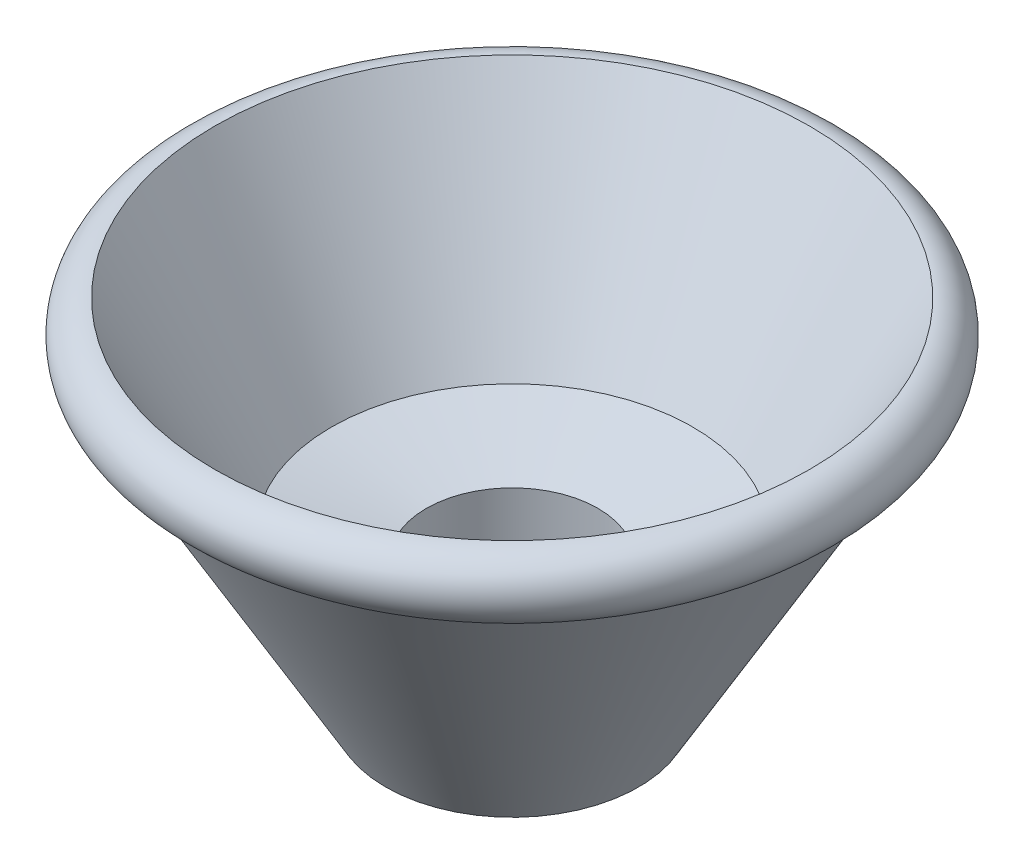
SolidWorks part; units mm, degrees
ref_plane "前视基准面" through (0, 0, 0) normal (0, 0, 1) x (1, 0, 0)
ref_plane "上视基准面" through (0, 0, 0) normal (0, 1, 0) x (1, 0, 0)
ref_plane "右视基准面" through (0, 0, 0) normal (1, 0, 0) x (0, 0, -1)
sketch "草图2" plane through (0, 0, 0) normal (0, 0, 1) x (1, 0, 0)
  line L0 (0, -55.2667) -> (0, 55.2667) construction
  line L1 (0, 0) -> (-4.6188, 8)
  line L4 (-4.6188, 8) -> (0, 8)
  line L5 (0, 8) -> (0, 0)
  point P4 (0, 0)
  dimension "D1" = 30
  dimension "D2" = 8
  dimension "D3" = 4.6188
revolve "旋转1" add sketch "草图2" angle 360 about L0
sketch "草图4" plane through (0, 0, 0) normal (0, 0, 1) x (1, 0, 0)
  line L0 (0, 7.1952) -> (0, 8.8048) construction
  line L2 (0, 8) -> (-4.0415, 8)
  line L3 (4.6188, 8) -> (-4.6188, 8) construction
  line L4 (-4.0415, 8) -> (0, 1)
  line L5 (0, 1) -> (0, 8)
  point P3 (0, 8)
  dimension "D1" = 30
  dimension "D2" = 7
sketch "草图5" plane through (0, 0, 0) normal (0, 1, 0) x (1, 0, 0)
  circle A0 centre (0, 0) radius 0.31
  dimension "D1" = 0.62
extrude "凸台-拉伸1" add sketch "草图5" against normal blind 6 and the other way blind 0.6
sketch "草图7" plane through (0, -6, 0) normal (0, -1, 0) x (1, 0, 0)
  circle A0 centre (0, 0) radius 0.28
  dimension "D1" = 0.56
extrude "切除-拉伸2" cut sketch "草图7" against normal through all
revolve "切除-旋转2" cut sketch "草图4" angle 360 about L0
sketch "草图10" plane through (0, 0, 0) normal (0, 0, 1) x (1, 0, 0)
  line L0 (-4.6188, 8) -> (-4.6188, 9) construction
  line L1 (-4.6188, 9) -> (4.6188, 8) construction
  line L2 (4.6188, 8) -> (4.6188, 9) construction
  line L3 (4.6188, 9) -> (-4.6188, 9) construction
  line L4 (-4.6188, 8.5) -> (4.9727, 8.5) construction
  line L5 (-4.6188, 8) -> (-4.0415, 8)
  line L6 (-4.0415, 8) -> (-4.0415, 9)
  line L7 (-4.0415, 9) -> (-4.6188, 9)
  line L8 (0, 0) -> (0, 12.6323) construction
  arc A0 (-4.6188, 9) -> (-4.6188, 8) centre (-4.6188, 8.5) ccw
  dimension "D1" = 1
revolve "旋转3" add sketch "草图10" angle 360 about L8 region at (-4.5329, 8.5, 0)
sketch "草图11" plane through (0, 0, 0) normal (0, 0, 1) x (1, 0, 0)
  line L0 (0, 0) -> (0, 13.3083) construction
  line L1 (-4.0415, 8) -> (-4.9325, 9.5433)
  line L2 (-4.9325, 9.5433) -> (-1.7812, 9.5433)
  line L3 (-1.7812, 9.5433) -> (-1.7812, 8)
  line L4 (-1.7812, 8) -> (-4.0415, 8)
  dimension "D1" = 30
revolve "切除-旋转3" cut sketch "草图11" angle 360 about L0
sketch "草图14" plane through (0, 0, 0) normal (0, 0, 1) x (1, 0, 0)
  line L0 (-0.325, 3.4014) -> (-0.325, 3.7514) construction
  line L1 (-4.6188, 8) -> (-0.31, 0.5369) construction
  line L2 (-0.325, 3.7514) -> (-2.1659, 3.7514) construction
  line L3 (0.325, 3.4014) -> (0.325, 3.7514)
  line L4 (-0.325, 3.4014) -> (0.325, 3.4014) construction
  line L5 (0.325, 3.7514) -> (2.1659, 3.7514)
  line L7 (0, 0) -> (0, 6.3714) construction
  line L9 (0.31, 0.5369) -> (4.6188, 8) construction
  line L10 (0.325, 3.4014) -> (1.9638, 3.4014)
  line L11 (2.1659, 3.7514) -> (1.9638, 3.4014)
  dimension "D1" = 0.65
  dimension "D2" = 0.35
  dimension "D3" = 0.35
revolve "旋转4" add sketch "草图14" angle 360 about L7
sketch "草图16" plane through (0, 0, 0) normal (0, 0, 1) x (1, 0, 0)
  line L0 (1.3865, 3.4014) -> (4.7356, 3.4014)
  line L1 (4.7356, 3.4014) -> (4.7356, -6.5649)
  line L2 (4.7356, -6.5649) -> (-5.8301, -6.5649)
  line L3 (-5.8301, -6.5649) -> (-5.8301, 3.4014)
  line L4 (-5.8301, 3.4014) -> (1.3865, 3.4014)
extrude "切除-拉伸3" cut sketch "草图16" against normal blind 10 and the other way blind 10
sketch "草图21" plane through (0, 0, 0) normal (0, 0, 1) x (1, 0, 0)
  line L0 (4.6188, 9) -> (1.5885, 3.7514) construction
  line L1 (1.5885, 3.7514) -> (1.5885, 5.3412)
  line L2 (1.5885, 3.7514) -> (2.6981, 5.6732)
  line L5 (0, 0.0626) -> (0, 7.1774) construction
  line L9 (1.2716, 4.9155) -> (1.2716, 5.5074) construction
  line L10 (1.5885, 5.3412) -> (1.3337, 5.3412) construction
  line L11 (1.3337, 5.3412) -> (2.6981, 5.6732) construction
  line L12 (2.6981, 5.6732) -> (2.8056, 5.8594)
  line L13 (2.8056, 5.8594) -> (1.3337, 5.5012)
  line L14 (1.3337, 5.5012) -> (1.5885, 5.5012)
  line L15 (1.5885, 5.5012) -> (1.5885, 5.3412)
  dimension "D1" = 0.16
revolve "旋转5" add sketch "草图21" angle 360 about L5
